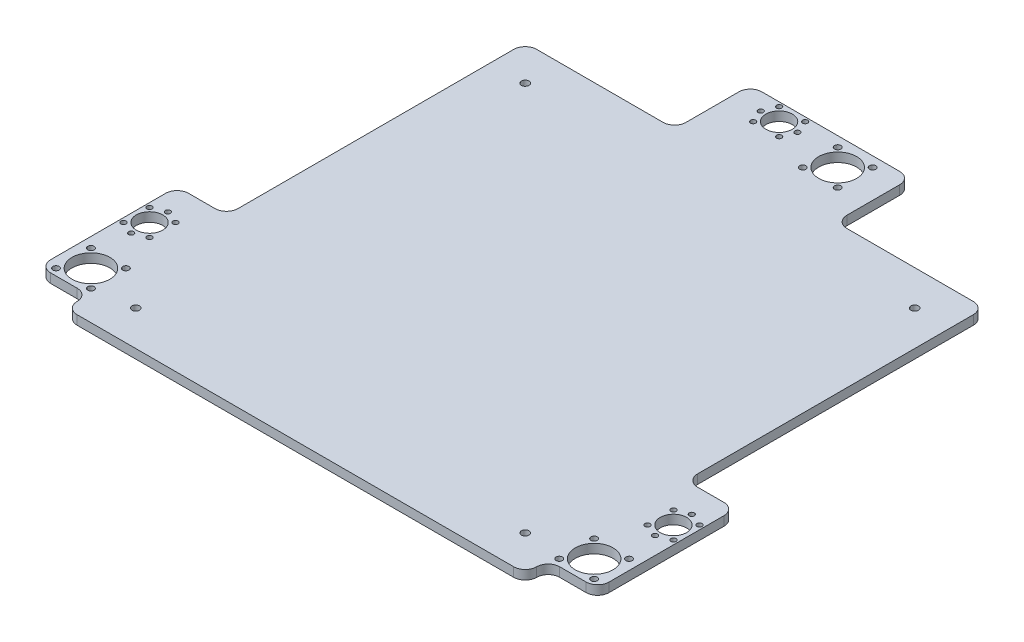
SolidWorks part; units mm, degrees
material "Plain Carbon Steel"
ref_plane "Front Plane" through (0, 0, 0) normal (0, 0, 1) x (1, 0, 0)
ref_plane "Top Plane" through (0, 0, 0) normal (0, 1, 0) x (1, 0, 0)
ref_plane "Right Plane" through (0, 0, 0) normal (1, 0, 0) x (0, 0, -1)
sketch "Sketch1" plane through (0, 0, 0) normal (0, 1, 0) x (1, 0, 0)
  line L0 (-243, -200) -> (243, -200)
  line L1 (-169.5, 169.5) -> (169.5, 169.5)
  line L2 (-169.5, 169.5) -> (-169.5, -169.5)
  line L3 (-169.5, -169.5) -> (169.5, -169.5)
  line L4 (169.5, 169.5) -> (169.5, -169.5)
  line L5 (-169.5, 169.5) -> (169.5, -169.5) construction
  line L6 (-169.5, -169.5) -> (169.5, 169.5) construction
  line L7 (-243, -200) -> (-243, 246)
  line L8 (-243, 246) -> (243, 246)
  line L9 (243, 246) -> (243, -200)
  line L10 (0, 0) -> (0, -200)
  point P0 (0, 0)
  dimension "D1" = 339
  dimension "D2" = 446
  dimension "D3" = 486
  dimension "D4" = 200
sketch "Sketch2" plane through (0, 0, 0) normal (0, 1, 0) x (1, 0, 0)
  line L0 (243, 246) -> (243, -200) construction
  line L1 (-243, 246) -> (243, 246) construction
  line L2 (-243, -200) -> (-243, 246) construction
  line L3 (-243, -200) -> (243, -200) construction
  line L4 (243, 246) -> (243, -200)
  line L5 (-243, 246) -> (243, 246)
  line L6 (-243, -200) -> (-243, 246)
  line L7 (-243, -200) -> (243, -200)
extrude "Boss-Extrude1" add sketch "Sketch2" along normal blind 8
sketch "Sketch3" plane through (0, 8, 0) normal (0, 1, 0) x (1, 0, 0)
  circle A0 centre (-203.7972, -194.2028) radius 2.75 construction
  circle A1 centre (-234.2028, -194.2028) radius 2.75 construction
  circle A2 centre (-234.2028, -163.7972) radius 2.75 construction
  circle A3 centre (-203.7972, -163.7972) radius 2.75 construction
  circle A4 centre (-203.7972, -194.2028) radius 2.75
  circle A5 centre (-234.2028, -194.2028) radius 2.75
  circle A6 centre (-234.2028, -163.7972) radius 2.75
  circle A7 centre (-203.7972, -163.7972) radius 2.75
  circle A8 centre (-239.3137, -107.6863) radius 2.35 construction
  circle A9 centre (-239.3137, -107.6863) radius 2.35 construction
  circle A10 centre (-239.3137, -130.3137) radius 2.35 construction
  circle A11 centre (-239.3137, -130.3137) radius 2.35 construction
  circle A12 centre (-228, -135) radius 2.35 construction
  circle A13 centre (-228, -135) radius 2.35 construction
  circle A14 centre (-216.6863, -130.3137) radius 2.35 construction
  circle A15 centre (-216.6863, -130.3137) radius 2.35 construction
  circle A16 centre (-216.6863, -107.6863) radius 2.35 construction
  circle A17 centre (-216.6863, -107.6863) radius 2.35 construction
  circle A18 centre (-228, -103) radius 2.35 construction
  circle A19 centre (-228, -103) radius 2.35 construction
  circle A20 centre (-239.3137, -107.6863) radius 2.35
  circle A21 centre (-239.3137, -107.6863) radius 2.35
  circle A22 centre (-239.3137, -130.3137) radius 2.35
  circle A23 centre (-239.3137, -130.3137) radius 2.35
  circle A24 centre (-228, -135) radius 2.35
  circle A25 centre (-228, -135) radius 2.35
  circle A26 centre (-216.6863, -130.3137) radius 2.35
  circle A27 centre (-216.6863, -130.3137) radius 2.35
  circle A28 centre (-216.6863, -107.6863) radius 2.35
  circle A29 centre (-216.6863, -107.6863) radius 2.35
  circle A30 centre (-228, -103) radius 2.35
  circle A31 centre (-228, -103) radius 2.35
  circle A32 centre (-228, -119) radius 11 construction
  circle A33 centre (-219, -179) radius 16 construction
  circle A34 centre (-228, -119) radius 11
  circle A35 centre (-219, -179) radius 16
  circle A36 centre (-18.6863, 242.3137) radius 2.35 construction
  circle A37 centre (-18.6863, 242.3137) radius 2.35 construction
  circle A38 centre (-41.3137, 242.3137) radius 2.35 construction
  circle A39 centre (-41.3137, 242.3137) radius 2.35 construction
  circle A40 centre (-46, 231) radius 2.35 construction
  circle A41 centre (-46, 231) radius 2.35 construction
  circle A42 centre (-41.3137, 219.6863) radius 2.35 construction
  circle A43 centre (-41.3137, 219.6863) radius 2.35 construction
  circle A44 centre (-18.6863, 219.6863) radius 2.35 construction
  circle A45 centre (-18.6863, 219.6863) radius 2.35 construction
  circle A46 centre (-14, 231) radius 2.35 construction
  circle A47 centre (-14, 231) radius 2.35 construction
  circle A48 centre (-18.6863, 242.3137) radius 2.35
  circle A49 centre (-18.6863, 242.3137) radius 2.35
  circle A50 centre (-41.3137, 242.3137) radius 2.35
  circle A51 centre (-41.3137, 242.3137) radius 2.35
  circle A52 centre (-46, 231) radius 2.35
  circle A53 centre (-46, 231) radius 2.35
  circle A54 centre (-41.3137, 219.6863) radius 2.35
  circle A55 centre (-41.3137, 219.6863) radius 2.35
  circle A56 centre (-18.6863, 219.6863) radius 2.35
  circle A57 centre (-18.6863, 219.6863) radius 2.35
  circle A58 centre (-14, 231) radius 2.35
  circle A59 centre (-14, 231) radius 2.35
  circle A60 centre (-30, 231) radius 11 construction
  circle A61 centre (30, 222) radius 16 construction
  circle A62 centre (45.2028, 237.2028) radius 2.75 construction
  circle A63 centre (14.7972, 237.2028) radius 2.75 construction
  circle A64 centre (14.7972, 206.7972) radius 2.75 construction
  circle A65 centre (45.2028, 206.7972) radius 2.75 construction
  circle A66 centre (-30, 231) radius 11
  circle A67 centre (30, 222) radius 16
  circle A68 centre (45.2028, 237.2028) radius 2.75
  circle A69 centre (14.7972, 237.2028) radius 2.75
  circle A70 centre (14.7972, 206.7972) radius 2.75
  circle A71 centre (45.2028, 206.7972) radius 2.75
hole_wizard "M5 Clearance Hole1" positions "Sketch4" profile "Sketch5" hole size "M5" standard "ANSI Metric" end condition through all
sketch "Sketch4" plane through (0, 8, 0) normal (0, 1, 0) x (1, 0, 0)
  point P0 (-234.2028, -163.7972)
  point P3 (-203.7972, -163.7972)
  point P6 (-203.7972, -194.2028)
  point P9 (-234.2028, -194.2028)
sketch "Sketch5" plane through (-234.2028, 8, 163.7972) normal (1, 0, 0) x (0, 0, 1)
  line L0 (0, 0) -> (0, 8)
  line L1 (0, 8) -> (2.75, 8)
  line L2 (2.75, 8) -> (2.75, 0)
  line L5 (2.75, 0) -> (0, 0)
  line L11 (0, -6.35) -> (0, 107.95) construction
  dimension "Thru Hole Dia." = 5.5
  dimension "Thru Hole Depth" = 8
hole_wizard "M4 Clearance Hole1" positions "Sketch6" profile "Sketch7" hole size "M4" standard "ANSI Metric" end condition through all
sketch "Sketch6" plane through (0, 8, 0) normal (0, 1, 0) x (1, 0, 0)
  point P0 (-228, -135)
  point P3 (-216.6863, -130.3137)
  point P6 (-216.6863, -107.6863)
  point P9 (-228, -103)
  point P12 (-239.3137, -107.6863)
  point P15 (-239.3137, -130.3137)
sketch "Sketch7" plane through (-228, 8, 135) normal (1, 0, 0) x (0, 0, 1)
  line L0 (0, 0) -> (0, 8)
  line L1 (0, 8) -> (2.25, 8)
  line L2 (2.25, 8) -> (2.25, 0)
  line L5 (2.25, 0) -> (0, 0)
  line L11 (0, -6.35) -> (0, 107.95) construction
  dimension "Thru Hole Dia." = 4.5
  dimension "Thru Hole Depth" = 8
sketch "Sketch8" plane through (0, 8, 0) normal (0, 1, 0) x (1, 0, 0)
  circle A0 centre (-228, -119) radius 11.5
  circle A1 centre (-219, -179) radius 16.5
  circle A2 centre (-219, -179) radius 16 construction
  circle A3 centre (-228, -119) radius 11 construction
  dimension "D1" = 0.5
  dimension "D2" = 0.5
extrude "Cut-Extrude1" cut sketch "Sketch8" against normal through all
mirror "Mirror1" about plane through (0, 0, 0) normal (1, 0, 0) of "Cut-Extrude1", "M4 Clearance Hole1", "M5 Clearance Hole1"
hole_wizard "M5 Clearance Hole2" positions "Sketch9" profile "Sketch10" hole size "M5" standard "ANSI Metric" end condition through all
sketch "Sketch9" plane through (0, 8, 0) normal (0, 1, 0) x (1, 0, 0)
  point P0 (45.2028, 206.7972)
  point P3 (14.7972, 206.7972)
  point P6 (14.7972, 237.2028)
  point P9 (45.2028, 237.2028)
sketch "Sketch10" plane through (45.2028, 8, -206.7972) normal (1, 0, 0) x (0, 0, 1)
  line L0 (0, 0) -> (0, 8)
  line L1 (0, 8) -> (2.75, 8)
  line L2 (2.75, 8) -> (2.75, 0)
  line L5 (2.75, 0) -> (0, 0)
  line L11 (0, -6.35) -> (0, 107.95) construction
  dimension "Thru Hole Dia." = 5.5
  dimension "Thru Hole Depth" = 8
hole_wizard "M4 Clearance Hole2" positions "Sketch11" profile "Sketch12" hole size "M4" standard "ANSI Metric" end condition through all
sketch "Sketch11" plane through (0, 8, 0) normal (0, 1, 0) x (1, 0, 0)
  point P0 (-41.3137, 219.6863)
  point P3 (-46, 231)
  point P6 (-41.3137, 242.3137)
  point P9 (-18.6863, 242.3137)
  point P12 (-14, 231)
  point P15 (-18.6863, 219.6863)
sketch "Sketch12" plane through (-41.3137, 8, -219.6863) normal (1, 0, 0) x (0, 0, 1)
  line L0 (0, 0) -> (0, 8)
  line L1 (0, 8) -> (2.25, 8)
  line L2 (2.25, 8) -> (2.25, 0)
  line L5 (2.25, 0) -> (0, 0)
  line L11 (0, -6.35) -> (0, 107.95) construction
  dimension "Thru Hole Dia." = 4.5
  dimension "Thru Hole Depth" = 8
sketch "Sketch13" plane through (0, 8, 0) normal (0, 1, 0) x (1, 0, 0)
  circle A0 centre (-30, 231) radius 11.5
  circle A1 centre (30, 222) radius 16.5
  circle A3 centre (-228, -119) radius 11.5 construction
  circle A4 centre (-219, -179) radius 16.5 construction
extrude "Cut-Extrude2" cut sketch "Sketch13" against normal through all
sketch "Sketch17" plane through (0, 8, 0) normal (0, 1, 0) x (1, 0, 0)
  line L1 (154.5, 139.5) -> (-154.5, 139.5)
  line L2 (154.5, 139.5) -> (154.5, -139.5)
  line L3 (154.5, -139.5) -> (-154.5, -139.5)
  line L4 (-154.5, 139.5) -> (-154.5, -139.5)
  line L5 (154.5, 139.5) -> (-154.5, -139.5) construction
  line L6 (154.5, -139.5) -> (-154.5, 139.5) construction
  point P0 (0, 0)
  dimension "D1" = 15
  dimension "D2" = 30
extrude "Cut-Extrude3" [suppressed] cut sketch "Sketch17" against normal through all
sketch "Sketch18" plane through (0, 8, 0) normal (0, 1, 0) x (1, 0, 0)
  line L0 (-243, -200) -> (243, -200) construction
  line L1 (-154.5, -200) -> (154.5, -200)
  line L2 (-154.5, -200) -> (-154.5, -169.5)
  line L3 (-154.5, -169.5) -> (154.5, -169.5)
  line L4 (154.5, -200) -> (154.5, -169.5)
  line L5 (-169.5, -169.5) -> (169.5, -169.5) construction
  line L6 (0, -169.5) -> (0, 0) construction
  dimension "D1" = 15
extrude "Cut-Extrude4" [suppressed] cut sketch "Sketch18" against normal through all
sketch "Sketch19" plane through (0, 8, 0) normal (0, 1, 0) x (1, 0, 0)
  line L0 (-243, -80) -> (-200, -80)
  line L1 (-243, 246) -> (-243, -200) construction
  line L2 (-200, -80) -> (-200, 180)
  line L3 (-200, 180) -> (-70, 180)
  line L4 (-70, 180) -> (-70, 246)
  line L5 (243, 246) -> (-243, 246) construction
  line L6 (0, 0) -> (0, -200) construction
  line L7 (-243, -200) -> (243, -200) construction
  line L8 (-243, -80) -> (-243, 246)
  line L9 (-243, 246) -> (-70, 246)
  dimension "D1" = 200
  dimension "D2" = 180
  dimension "D3" = 70
  dimension "D4" = 120
extrude "Cut-Extrude5" cut sketch "Sketch19" against normal through all
mirror "Mirror2" about plane through (0, 0, 0) normal (1, 0, 0) of "Cut-Extrude5"
sketch "Sketch20" plane through (0, 8, 0) normal (0, 1, 0) x (1, 0, 0)
  line L0 (-200, -80) -> (-200, 180) construction
  line L1 (200, 180) -> (-200, 180)
  line L2 (200, 180) -> (200, -220)
  line L3 (200, -220) -> (-200, -220)
  line L4 (-200, 180) -> (-200, -220)
  dimension "D1" = 400
extrude "Boss-Extrude2" add sketch "Sketch20" against normal up to surface (8 mm away) up to face at (-30, 0, -219.5)
fillet "Fillet1" [suppressed] radius 10
fillet "Fillet2" [suppressed] radius 20
fillet "Fillet3" radius 10 16 edges at (-70, 4, -180) (-200, 4, -180) (-200, 4, 80) (70, 4, -180) (200, 4, -180) (200, 4, 80) (-243, 4, 200) (-243, 4, 80) (243, 4, 200) (243, 4, 80) (-70, 4, -246) (70, 4, -246) (200, 4, 220) (200, 4, 200) (-200, 4, 220) (-200, 4, 200)
sketch "Sketch21" plane through (0, 8, 0) normal (0, 1, 0) x (1, 0, 0)
  line L0 (-200, -70) -> (-200, 170) construction
  line L1 (200, -220) -> (-200, -220)
  line L2 (200, -220) -> (200, 180)
  line L3 (200, 180) -> (-200, 180)
  line L4 (-200, -220) -> (-200, 180)
  line L5 (-190, 180) -> (-80, 180) construction
  line L6 (200, -70) -> (200, 170) construction
  line L7 (-190, -220) -> (190, -220) construction
  line L8 (-200, 180) -> (200, -220) construction
  line L10 (169.5, 149.5) -> (-169.5, 149.5)
  line L11 (169.5, 149.5) -> (169.5, -189.5)
  line L12 (169.5, -189.5) -> (-169.5, -189.5)
  line L13 (-169.5, 149.5) -> (-169.5, -189.5)
  line L14 (169.5, 149.5) -> (-169.5, -189.5) construction
  line L15 (169.5, -189.5) -> (-169.5, 149.5) construction
  point P12 (0, -20)
  dimension "D1" = 339
hole_wizard "M6 Clearance Hole1" positions "Sketch15" profile "Sketch16" hole size "M6" standard "ANSI Metric" end condition through all
sketch "Sketch15" plane through (0, 8, 0) normal (0, 1, 0) x (1, 0, 0)
  point P0 (-169.5, -189.5)
  point P2 (-169.5, 149.5)
  point P4 (169.5, 149.5)
  point P6 (169.5, -189.5)
  point P18 (0, 0)
  point P19 (169.5, 149.5)
  point P21 (0, 0)
  point P22 (169.5, -189.5)
  point P24 (0, 0)
  point P25 (-169.5, -189.5)
  point P27 (0, 0)
  point P28 (-169.5, 149.5)
sketch "Sketch16" plane through (-169.5, 8, 189.5) normal (1, 0, 0) x (0, 0, 1)
  line L0 (0, 0) -> (0, 8)
  line L1 (0, 8) -> (3.3, 8)
  line L2 (3.3, 8) -> (3.3, 0)
  line L5 (3.3, 0) -> (0, 0)
  line L11 (0, -6.35) -> (0, 107.95) construction
  dimension "Thru Hole Dia." = 6.6
  dimension "Thru Hole Depth" = 8
